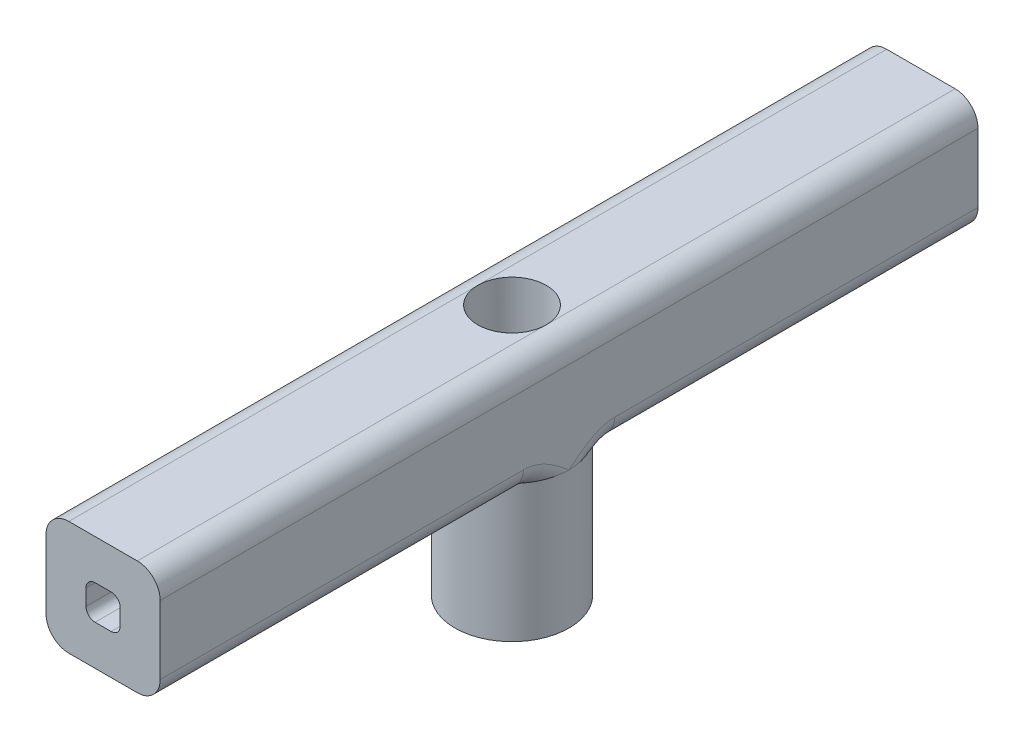
SolidWorks part; units mm, degrees
ref_plane "Ön Düzlem" through (0, 0, 0) normal (0, 0, 1) x (1, 0, 0)
ref_plane "Üst Düzlem" through (0, 0, 0) normal (0, 1, 0) x (1, 0, 0)
ref_plane "Sağ Düzlem" through (0, 0, 0) normal (1, 0, 0) x (0, 0, -1)
sketch "Çizim9" plane through (0, 0, 0) normal (0, 0, 1) x (1, 0, 0)
  line L1 (-12.5, 12.5) -> (12.5, 12.5)
  line L2 (-12.5, 12.5) -> (-12.5, -12.5)
  line L3 (-12.5, -12.5) -> (12.5, -12.5)
  line L4 (12.5, 12.5) -> (12.5, -12.5)
  line L5 (-12.5, 12.5) -> (12.5, -12.5) construction
  line L6 (-12.5, -12.5) -> (12.5, 12.5) construction
  point P0 (0, 0)
  dimension "D1" = 25
  dimension "D2" = 25
extrude "Yükseklik-Ekstrüzyon3" add sketch "Çizim9" against normal blind 279.0796
ref_plane "Düzlem5" through (0, 12.5, 0) normal (0, 1, 0) x (1, 0, 0)
sketch "Çizim10" plane through (0, 12.5, 0) normal (0, 1, 0) x (1, 0, 0)
  line L0 (0, 0) -> (0, 279.0796)
  line L1 (12.5, 279.0796) -> (-12.5, 279.0796) construction
  circle A0 centre (0, 139.5398) radius 12.5
extrude "Yükseklik-Ekstrüzyon4" add sketch "Çizim10" against normal blind 55 contours A0
sketch "Çizim11" plane through (0, 12.5, 0) normal (0, 1, 0) x (1, 0, 0)
  circle A0 centre (0, 139.5398) radius 7.5
extrude "Kes-Ekstrüzyon1" cut sketch "Çizim11" against normal blind 50
ref_plane "Düzlem6" through (0, -37.5, 0) normal (0, 1, 0) x (1, 0, 0)
sketch "Çizim12" plane through (0, -37.5, 0) normal (0, 1, 0) x (1, 0, 0)
  circle A0 centre (0, 139.5398) radius 3
extrude "Kes-Ekstrüzyon4" cut sketch "Çizim12" against normal through all
fillet "Radyus3" radius 5 6 edges at (12.5, -12.5, -69.7699) (-12.5, -12.5, -69.7699) (12.5, -12.5, -209.3097) (-12.5, -12.5, -209.3097) (-12.5, 12.5, -139.5398) (12.5, 12.5, -139.5398)
ref_plane "Düzlem7" through (0, 0, -279.0796) normal (0, 0, -1) x (-1, 0, 0)
sketch "Çizim13" plane through (0, 0, -279.0796) normal (0, 0, -1) x (-1, 0, 0)
  line L3 (13.75, 12.5) -> (-13.75, 12.5) construction
  line L5 (-7.5, 12.5) -> (7.5, 12.5)
  line L6 (-12.5, 7.5) -> (-12.5, -7.5)
  line L7 (-7.5, -12.5) -> (7.5, -12.5)
  line L8 (12.5, 7.5) -> (12.5, -7.5)
  line L9 (-12.5, 12.5) -> (12.5, -12.5) construction
  line L10 (-12.5, -12.5) -> (12.5, 12.5) construction
  arc A0 (7.5, -12.5) -> (12.5, -7.5) centre (7.5, -7.5) ccw
  arc A1 (-12.5, -7.5) -> (-7.5, -12.5) centre (-7.5, -7.5) ccw
  arc A2 (-7.5, 12.5) -> (-12.5, 7.5) centre (-7.5, 7.5) ccw
  arc A3 (12.5, 7.5) -> (7.5, 12.5) centre (7.5, 7.5) ccw
  dimension "D1" = 5
extrude "Kes-Ekstrüzyon5" cut sketch "Çizim13" against normal blind 50
ref_plane "Düzlem8" through (0, 0, 0) normal (0, 0, 1) x (1, 0, 0)
sketch "Çizim14" plane through (0, 0, 0) normal (0, 0, 1) x (1, 0, 0)
  line L1 (-7.5, 12.5) -> (7.5, 12.5)
  line L2 (-12.5, 7.5) -> (-12.5, -7.5)
  line L3 (-7.5, -12.5) -> (7.5, -12.5)
  line L4 (12.5, 7.5) -> (12.5, -7.5)
  line L5 (-12.5, 12.5) -> (12.5, -12.5) construction
  line L6 (-12.5, -12.5) -> (12.5, 12.5) construction
  arc A0 (-12.5, -7.5) -> (-7.5, -12.5) centre (-7.5, -7.5) ccw
  arc A1 (7.5, -12.5) -> (12.5, -7.5) centre (7.5, -7.5) ccw
  arc A2 (7.5, 12.5) -> (12.5, 7.5) centre (7.5, 7.5) cw
  arc A3 (-7.5, 12.5) -> (-12.5, 7.5) centre (-7.5, 7.5) ccw
  point P0 (0, 0)
  dimension "D1" = 5
extrude "Kes-Ekstrüzyon6" cut sketch "Çizim14" against normal blind 50
ref_plane "Düzlem9" through (0, 0, -229.0796) normal (0, 0, -1) x (-1, 0, 0)
sketch "Çizim15" plane through (0, 0, -229.0796) normal (0, 0, -1) x (-1, 0, 0)
  line L1 (-1.75, 3.75) -> (1.75, 3.75)
  line L2 (-3.75, 1.75) -> (-3.75, -1.75)
  line L3 (-1.75, -3.75) -> (1.75, -3.75)
  line L4 (3.75, 1.75) -> (3.75, -1.75)
  line L5 (-3.75, 3.75) -> (3.75, -3.75) construction
  line L6 (-3.75, -3.75) -> (3.75, 3.75) construction
  arc A0 (1.75, -3.75) -> (3.75, -1.75) centre (1.75, -1.75) ccw
  arc A1 (-3.75, -1.75) -> (-1.75, -3.75) centre (-1.75, -1.75) ccw
  arc A2 (-1.75, 3.75) -> (-3.75, 1.75) centre (-1.75, 1.75) ccw
  arc A3 (1.75, 3.75) -> (3.75, 1.75) centre (1.75, 1.75) cw
  point P0 (0, 0)
  dimension "D1" = 2
extrude "Kes-Ekstrüzyon7" cut sketch "Çizim15" against normal blind 7.5
ref_plane "Düzlem10" through (0, 0, -50) normal (0, 0, 1) x (1, 0, 0)
sketch "Çizim16" plane through (0, 0, -50) normal (0, 0, 1) x (1, 0, 0)
  line L1 (-1.75, 3.75) -> (1.75, 3.75)
  line L2 (-3.75, 1.75) -> (-3.75, -1.75)
  line L3 (-1.75, -3.75) -> (1.75, -3.75)
  line L4 (3.75, 1.75) -> (3.75, -1.75)
  line L5 (-3.75, 3.75) -> (3.75, -3.75) construction
  line L6 (-3.75, -3.75) -> (3.75, 3.75) construction
  arc A0 (-3.75, -1.75) -> (-1.75, -3.75) centre (-1.75, -1.75) ccw
  arc A1 (1.75, -3.75) -> (3.75, -1.75) centre (1.75, -1.75) ccw
  arc A2 (1.75, 3.75) -> (3.75, 1.75) centre (1.75, 1.75) cw
  arc A3 (-1.75, 3.75) -> (-3.75, 1.75) centre (-1.75, 1.75) ccw
  point P0 (0, 0)
  dimension "D1" = 2
extrude "Kes-Ekstrüzyon8" cut sketch "Çizim16" against normal blind 7.5
